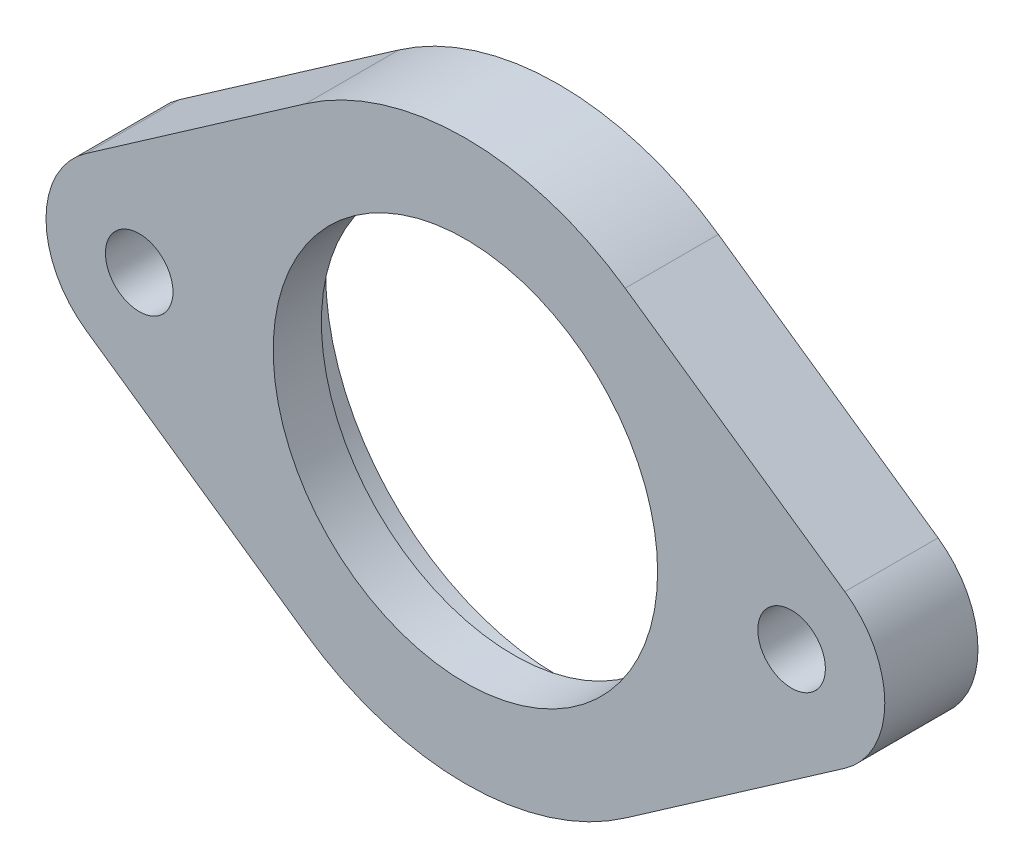
SolidWorks part; units mm, degrees
material "ABS"
ref_plane "Front Plane" through (0, 0, 0) normal (0, 0, 1) x (1, 0, 0)
ref_plane "Top Plane" through (0, 0, 0) normal (0, 1, 0) x (1, 0, 0)
ref_plane "Right Plane" through (0, 0, 0) normal (1, 0, 0) x (0, 0, -1)
sketch "Sketch1" plane through (0, 0, 0) normal (0, 0, 1) x (1, 0, 0)
  line L0 (-14, 0) -> (14, 0)
  line L1 (-6.8571, -9.8478) -> (-16.2857, -3.2826)
  line L2 (-6.8571, 9.8478) -> (-16.2857, 3.2826)
  line L3 (6.8571, 9.8478) -> (16.2857, 3.2826)
  line L4 (6.8571, -9.8478) -> (16.2857, -3.2826)
  circle A0 centre (0, 0) radius 8.25
  circle A1 centre (0, 0) radius 10
  circle A2 centre (0, 0) radius 12
  circle A3 centre (-14, 0) radius 4
  circle A4 centre (14, 0) radius 4
  point P7 (0, 0)
  dimension "D1" = 16.5
  dimension "D2" = 20
  dimension "D3" = 2
  dimension "D4" = 8
  dimension "D5" = 28
extrude "Boss-Extrude1" add sketch "Sketch1" along normal blind 4 contours A3 L0 A2 L2 | A3 L1 A2 L0 | A3 | A4 L3 A2 L0 | A4 | A4 L0 A2 L4 | A2 region at (14.6154, 0, 0) region at (11.8356, 5.4155, 0) region at (11.8356, -5.4155, 0) region at (-14.6154, 0, 0) region at (-11.8356, 5.4155, 0) region at (-11.8356, -5.4155, 0)
extrude "Cut-Extrude1" cut sketch "Sketch1<4>" against normal through all both and the other way through all contours L0 A0 | L0 A0 region at (0, -3.5014, 0) region at (0, 3.5014, 0)
sketch "Sketch1<4>" plane through (0, 0, 0) normal (0, 0, 1) x (1, 0, 0) same geometry as "Sketch1"
extrude "Cut-Extrude2" cut sketch "Sketch1<6>" along normal blind 1.93 and the other way through all contours A1
sketch "Sketch1<6>" plane through (0, 0, 0) normal (0, 0, 1) x (1, 0, 0) same geometry as "Sketch1"
sketch "Sketch2" plane through (0, 0, 4) normal (0, 0, 1) x (1, 0, 0)
  point P0 (-14, 0)
  point P3 (14, 0)
hole_wizard "M2.5 Clearance Hole1" positions "Sketch2" profile "Sketch3" hole size "M2.5" standard "ANSI Metric" end condition through all
sketch "Sketch3" plane through (-14, 0, 4) normal (1, 0, 0) x (0, -1, 0)
  line L0 (0, 0) -> (0, 4)
  line L1 (0, 4) -> (1.45, 4)
  line L2 (1.45, 4) -> (1.45, 0)
  line L5 (1.45, 0) -> (0, 0)
  line L11 (0, -6.35) -> (0, 107.95) construction
  dimension "Thru Hole Dia." = 2.9
  dimension "Thru Hole Depth" = 4
